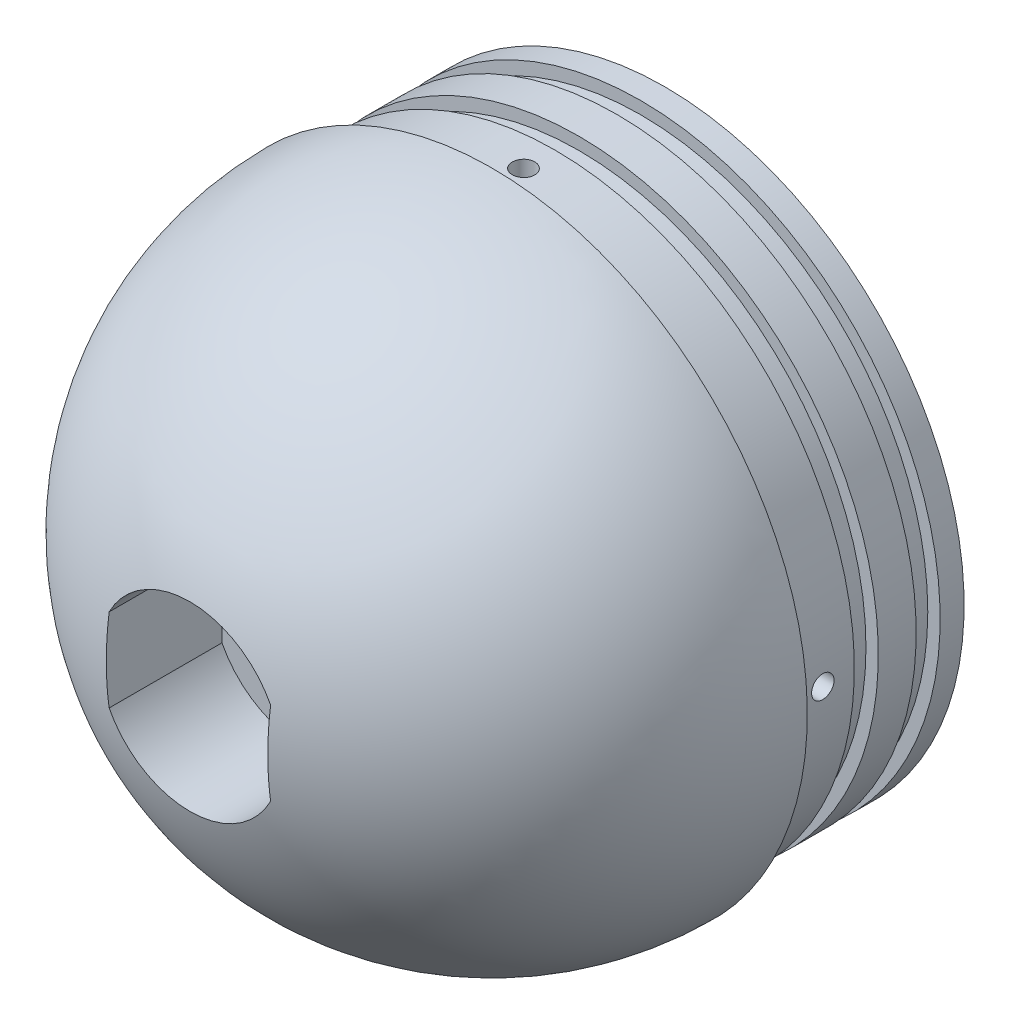
SolidWorks part; units mm, degrees
material "6061-T6 (SS)"
ref_plane "XY" through (0, 0, 0) normal (0, 0, 1) x (1, 0, 0)
ref_plane "XZ" through (0, 0, 0) normal (0, 1, 0) x (1, 0, 0)
ref_plane "YZ" through (0, 0, 0) normal (1, 0, 0) x (0, 0, -1)
ref_axis "X" through (-34.925, 0, 0) along (1, 0, 0)
ref_axis "Y" through (0, -34.925, 0) along (0, 1, 0)
ref_axis "Z" through (0, 0, 50.4955) along (0, 0, -1)
sketch "Sketch2" plane through (0, 0, 0) normal (1, 0, 0) x (0, 0, -1)
  line L2 (-17.399, 30.1371) -> (-11.049, 30.1371)
  line L3 (-11.049, 30.1371) -> (-11.049, 28.8925)
  line L4 (-11.049, 28.8925) -> (-8.636, 28.8925)
  line L5 (-8.636, 28.8925) -> (-8.636, 30.1371)
  line L6 (-8.636, 30.1371) -> (-4.826, 30.1371)
  line L7 (-4.826, 30.1371) -> (-4.826, 28.8925)
  line L8 (-4.826, 28.8925) -> (-2.413, 28.8925)
  line L9 (-2.413, 28.8925) -> (-2.413, 30.1371)
  line L10 (-2.413, 30.1371) -> (0, 30.1371)
  line L11 (0, 30.1371) -> (0, 0)
  line L12 (0, 0) -> (-17.399, 0)
  line L13 (-17.399, 30.1371) -> (-17.399, 0)
  dimension "D1" = 30.1371
  dimension "D2" = 28.8925
  dimension "D3" = 2.413
  dimension "D4" = 3.81
  dimension "D5" = 2.413
  dimension "D7" = 6.35
revolve "Revolve1" add sketch "Sketch2" angle 360 about L12
hole_wizard "#4-40 Tapped Hole1" positions "3DSketch1" profile "Sketch3" tap size "#4-40" standard "ANSI Inch"
sketch3d "3DSketch1"
  line L0 (0, 0, 0) -> (0, 0, 14.224)
  line L1 (0, 0, 14.224) -> (-30.1371, 0, 14.224)
  line L3 (30.1371, 0, 14.224) -> (0, -30.1371, 14.224)
  line L5 (0, -30.1371, 14.224) -> (-30.1371, 0, 14.224)
  line L9 (0, 0, 14.224) -> (0, -30.1371, 14.224)
  line L11 (0, 0, 14.224) -> (30.1371, 0, 14.224)
  line L13 (0, 0, 14.224) -> (0, 30.1371, 14.224)
  line L15 (0, -30.1371, 11.049) -> (0, -30.1371, 17.399)
  line L16 (0, 30.1371, 14.224) -> (-30.1371, 0, 14.224)
  line L18 (30.1371, 0, 14.224) -> (0, 30.1371, 14.224)
  circle A1 centre (0, 0, 11.049) radius 30.1371 construction
  circle A2 centre (0, 0, 17.399) radius 30.1371 construction
  point P5 (0, -30.1371, 14.224)
  point P7 (30.1371, 0, 14.224)
  point P20 (-30.1371, 0, 14.224)
  point P1370 (0, 0, -19.0881)
  point P1373 (0, 0, -12.7381)
  point P1390 (0, 30.1371, 14.224)
cosmetic thread "Hole Thread2" parameters "D1"=5.588, "D2"=2.8448
cosmetic thread "Hole Thread3" parameters "D1"=5.588, "D2"=2.8448
cosmetic thread "Hole Thread5" parameters "D1"=5.588, "D2"=2.8448
cosmetic thread "Hole Thread6" parameters "D1"=5.588, "D2"=2.8448
sketch "Sketch3" plane through (0, -30.1371, 14.224) normal (1, 0, 0) x (0, 0, -1)
  line L0 (0, 0) -> (0, 8.2992)
  line L1 (0, 8.2992) -> (1.1303, 7.62)
  line L2 (1.1303, 7.62) -> (1.1303, 0)
  line L5 (1.1303, 0) -> (0, 0)
  line L10 (0, 8.2992) -> (-1.1303, 7.62) construction
  line L11 (0, -6.35) -> (0, 107.95) construction
  dimension "Tap Drill Dia." = 2.2606
  dimension "Tap Drill Depth" = 7.62
  dimension "Drill Angle" = 118
sketch "Sketch6" plane through (0, 0, 0) normal (0, 1, 0) x (1, 0, 0)
  line L0 (0, -17.399) -> (31.75, -17.399)
  line L1 (-30.1371, -17.399) -> (30.1371, -17.399) construction
  line L2 (0, -17.399) -> (0, -49.149)
  arc A0 (0, -49.149) -> (31.75, -17.399) centre (0, -17.399) ccw
  dimension "D1" = 31.75
revolve "Revolve2" add sketch "Sketch6" angle 360 about L2
ref_plane "Plane1" through (0, 0, 49.149) normal (0, 0, 1) x (1, 0, 0)
sketch "Sketch8" plane through (0, 0, 49.149) normal (0, 0, 1) x (1, 0, 0)
  line L1 (-8.128, 4.1891) -> (8.128, 4.1891) construction
  line L2 (-8.128, 4.1891) -> (-8.128, -4.1891)
  line L3 (-8.128, -4.1891) -> (8.128, -4.1891) construction
  line L4 (8.128, 4.1891) -> (8.128, -4.1891)
  line L5 (-8.128, 4.1891) -> (8.128, -4.1891) construction
  line L6 (-8.128, -4.1891) -> (8.128, 4.1891) construction
  arc A0 (8.128, 4.1891) -> (-8.128, 4.1891) centre (0, 0) ccw
  arc A1 (-8.128, -4.1891) -> (8.128, -4.1891) centre (0, 0) ccw
  dimension "D1" = 18.288
  dimension "D2" = 16.256
extrude "Cut-Extrude1" cut sketch "Sketch8" against normal blind 12.7
sketch "Sketch9" plane through (0, 0, 36.449) normal (0, 0, 1) x (1, 0, 0)
  circle A0 centre (0, 0) radius 5.1
  dimension "D1" = 10.2
extrude "Cut-Extrude2" cut sketch "Sketch9" against normal through all
sketch "Sketch10" plane through (0, 0, 0) normal (0, 0, -1) x (-1, 0, 0)
  circle A0 centre (0, 0) radius 19.9478
extrude "Cut-Extrude3" cut sketch "Sketch10" against normal offset from surface (28.449 mm away) 8 up to face at (5.1, 0, 36.449)
hole_wizard "#8-32 Tapped Hole1" positions "Sketch11" profile "Sketch12" tap size "#8-32" standard "ANSI Inch"
sketch "Sketch11" plane through (0, 0, 28.449) normal (0, 0, -1) x (-1, 0, 0)
  line L1 (0, 0) -> (-5.1, 0) construction
  line L2 (-5.1, 0) -> (-19.9478, 0) construction
  line L5 (5.1, 0) -> (19.9478, 0) construction
  circle A0 centre (0, 0) radius 5.1 construction
  circle A1 centre (0, 0) radius 19.9478 construction
  point P25 (-12.5239, 0)
  point P27 (12.5239, 0)
cosmetic thread "Hole Thread7" parameters "D1"=8.382, "D2"=4.1656
cosmetic thread "Hole Thread8" parameters "D1"=8.382, "D2"=4.1656
sketch "Sketch12" plane through (-12.5239, 0, 28.449) normal (1, 0, 0) x (0, 1, 0)
  line L0 (0, 0) -> (0, 11.7058)
  line L1 (0, 11.7058) -> (1.7272, 10.668)
  line L2 (1.7272, 10.668) -> (1.7272, 0)
  line L5 (1.7272, 0) -> (0, 0)
  line L10 (0, 11.7058) -> (-1.7272, 10.668) construction
  line L11 (0, -6.35) -> (0, 107.95) construction
  dimension "Tap Drill Dia." = 3.4544
  dimension "Tap Drill Depth" = 10.668
  dimension "Drill Angle" = 118
sketch "Sketch13" plane through (0, 0, 28.449) normal (0, 0, -1) x (-1, 0, 0)
  circle A0 centre (0, 0) radius 19.9478
  circle A1 centre (0, 0) radius 19.9478 construction
extrude "Boss-Extrude1" [suppressed] add sketch "Sketch13" along normal blind 20.32 separate body
sketch "Sketch14" plane through (0, 0, 0) normal (0, 0, -1) x (-1, 0, 0)
  line L0 (-26.7745, -3.175) -> (-20.4245, -3.175)
  line L1 (-20.4245, -3.175) -> (-20.4245, 3.175)
  line L2 (-20.4245, 3.175) -> (-26.7745, 3.175)
  line L3 (0, 0) -> (-20.4245, 0) construction
  line L4 (-3.175, 26.7745) -> (-3.175, 20.4245)
  line L5 (-3.175, 20.4245) -> (3.175, 20.4245)
  line L6 (3.175, 20.4245) -> (3.175, 26.7745)
  line L7 (26.7745, 3.175) -> (20.4245, 3.175)
  line L8 (20.4245, 3.175) -> (20.4245, -3.175)
  line L9 (20.4245, -3.175) -> (26.7745, -3.175)
  line L10 (3.175, -26.7745) -> (3.175, -20.4245)
  line L11 (3.175, -20.4245) -> (-3.175, -20.4245)
  line L12 (-3.175, -20.4245) -> (-3.175, -26.7745)
  line L13 (0, 0) -> (0, 20.4245) construction
  arc A0 (-26.7745, -3.175) -> (-3.175, -26.7745) centre (0, 0) ccw
  circle A1 centre (0, 0) radius 30.1371 construction
  arc A2 (3.175, -26.7745) -> (26.7745, -3.175) centre (0, 0) ccw
  arc A3 (-3.175, 26.7745) -> (-26.7745, 3.175) centre (0, 0) ccw
  arc A4 (26.7745, 3.175) -> (3.175, 26.7745) centre (0, 0) ccw
  dimension "D1" = 3.175
  dimension "D2" = 6.35
  dimension "D3" = 6.35
  dimension "D4" = 4
extrude "Cut-Extrude4" cut sketch "Sketch14" against normal up to surface (28.449 mm away) up to face at (10.7967, 0, 28.449)
fillet "Fillet1" radius 6.858 8 edges at (26.7745, -3.175, 14.2245) (26.7745, 3.175, 14.2245) (3.175, 26.7745, 14.2245) (-3.175, 26.7745, 14.2245) (-26.7745, 3.175, 14.2245) (-26.7745, -3.175, 14.2245) (-3.175, -26.7745, 14.2245) (3.175, -26.7745, 14.2245)
